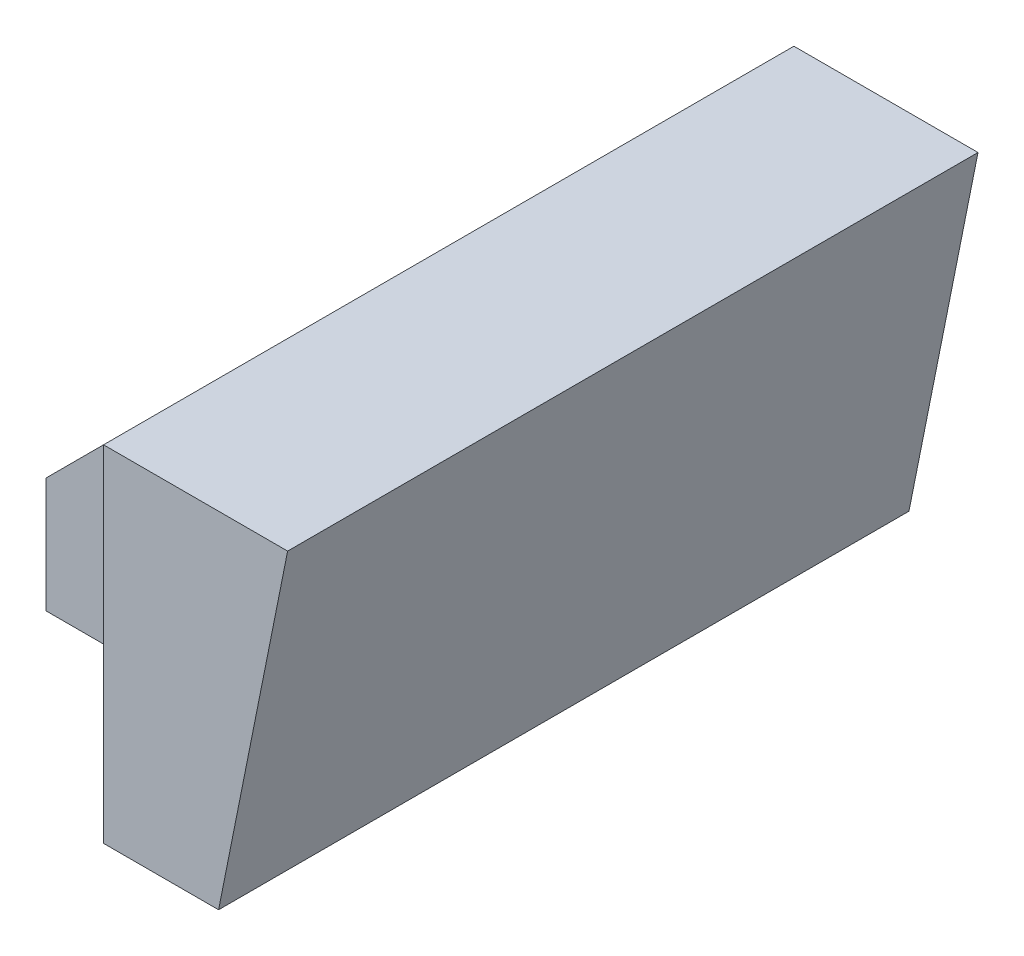
SolidWorks part; units mm, degrees
ref_plane "Alzado" through (0, 0, 0) normal (0, 0, 1) x (1, 0, 0)
ref_plane "Planta" through (0, 0, 0) normal (0, 1, 0) x (1, 0, 0)
ref_plane "Vista lateral" through (0, 0, 0) normal (1, 0, 0) x (0, 0, -1)
sketch "Croquis1" plane through (0, 0, 0) normal (0, 1, 0) x (1, 0, 0)
  line L1 (-4, -15) -> (4, -15)
  line L2 (-4, -15) -> (-4, 15)
  line L3 (-4, 15) -> (4, 15)
  line L4 (4, -15) -> (4, 15)
  line L5 (-4, -15) -> (4, 15) construction
  line L6 (-4, 15) -> (4, -15) construction
  point P0 (0, 0)
  dimension "D1" = 30
  dimension "D2" = 8
extrude "Saliente-Extruir1" add sketch "Croquis1" along normal blind 15
sketch "Croquis2" plane through (0, 0, 15) normal (0, 0, 1) x (1, 0, 0)
  line L0 (4, 15) -> (1, 0)
  line L1 (-4, 0) -> (4, 0) construction
  line L2 (1, 0) -> (4, 0)
  line L3 (4, 0) -> (4, 15)
  dimension "D1" = 5
extrude "Cortar-Extruir1" cut sketch "Croquis2" against normal through all
sketch "Croquis3" plane through (0, 0, 0) normal (0, 0, 1) x (1, 0, 0)
  line L1 (-14, 0) -> (-4, 0)
  line L2 (-4, 0) -> (-4, 15)
  line L3 (-14, 0) -> (-14, 5)
  line L4 (-14, 5) -> (-4, 15)
  dimension "D1" = 10
  dimension "D2" = 5
extrude "Saliente-Extruir2" add sketch "Croquis3" along normal mid plane 15
sketch "Croquis4" plane through (0, 15, 0) normal (0, 1, 0) x (1, 0, 0)
  line L0 (-14, -7.5) -> (-14, 7.5) construction
  line L1 (-14, 4.5) -> (-4, 4.5)
  line L2 (-14, 4.5) -> (-14, -4.5)
  line L3 (-14, -4.5) -> (-4, -4.5)
  line L4 (-4, 4.5) -> (-4, -4.5)
  line L5 (-4, -7.5) -> (-4, 7.5) construction
  line L6 (-4, 7.5) -> (-14, 7.5) construction
  line L7 (-4, -7.5) -> (-14, -7.5) construction
  dimension "D1" = 3
  dimension "D2" = 3
extrude "Cortar-Extruir2" cut sketch "Croquis4" against normal blind 10
sketch "Croquis5" plane through (0, 5, 0) normal (0, 1, 0) x (1, 0, 0)
  line L0 (-14, 4.5) -> (-4, -4.5) construction
  circle A0 centre (-9, 0) radius 1.6
  dimension "D1" = 3.2
extrude "Cortar-Extruir3" cut sketch "Croquis5" against normal through all
sketch "Croquis6" plane through (0, 0, 0) normal (0, -1, 0) x (1, 0, 0)
  line L0 (-8.4432, 1.5) -> (-4, 1.5)
  line L1 (-14, -1.5) -> (-9.5568, -1.5)
  line L2 (-14, -1.5) -> (-14, 1.5)
  line L3 (-14, 1.5) -> (-9.5568, 1.5)
  line L4 (-4, -1.5) -> (-4, 1.5)
  line L5 (-14, -1.5) -> (-4, 1.5) construction
  line L6 (-14, 1.5) -> (-4, -1.5) construction
  line L7 (-8.4432, -1.5) -> (-4, -1.5)
  circle A0 centre (-9, 0) radius 1.6 construction
  arc A1 (-9.5568, 1.5) -> (-9.5568, -1.5) centre (-9, 0) ccw
  arc A2 (-8.4432, -1.5) -> (-8.4432, 1.5) centre (-9, 0) ccw
  point P0 (-9, 0)
  dimension "D1" = 3
  dimension "D2" = 10
extrude "Saliente-Extruir3" add sketch "Croquis6" along normal blind 3.5
fillet "Redondeo1" radius 1 4 edges at (-9.5568, -1.75, -1.5) (-8.4432, -1.75, -1.5) (-8.4432, -1.75, 1.5) (-9.5568, -1.75, 1.5)
